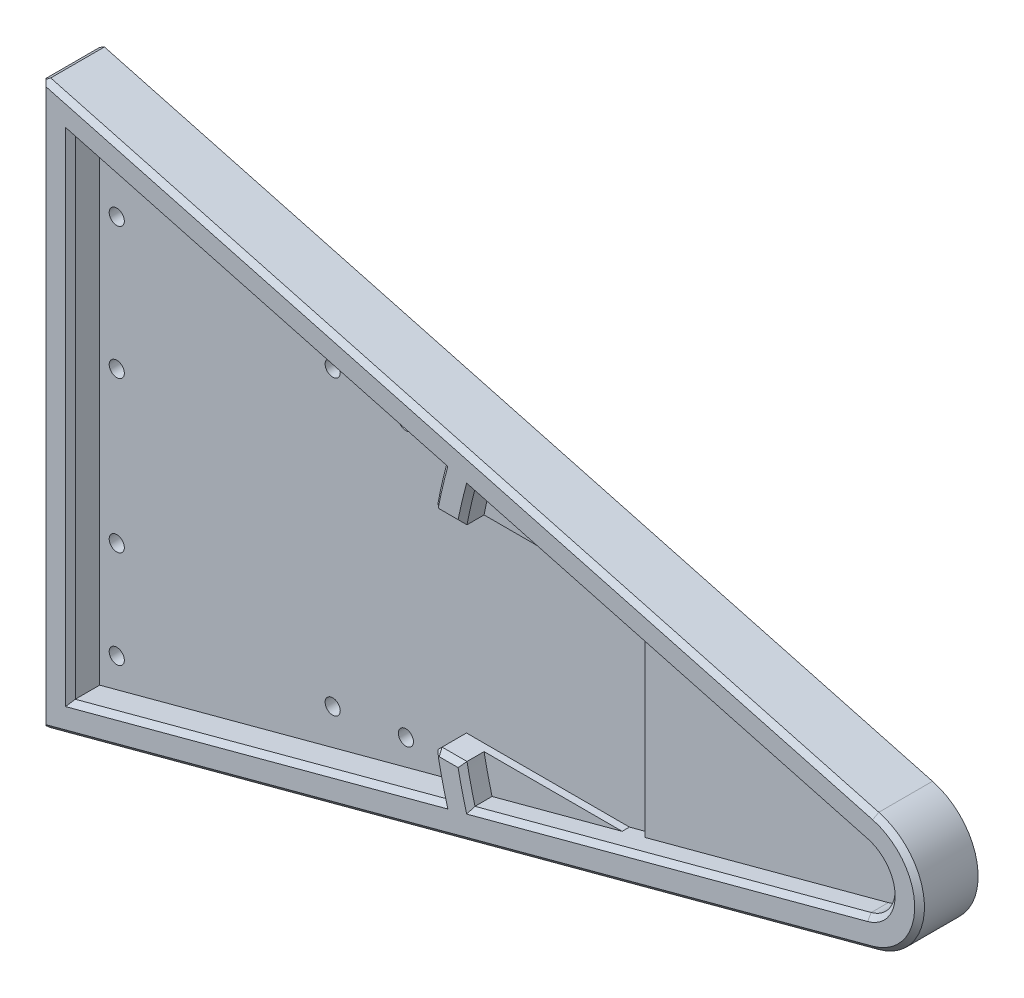
SolidWorks part; units mm, degrees
note: '?' marks a value the reader was unsure of. The reader was unsure of these and kept them because the rebuilt part matched: shared geometry of "Sketch3<3>".
ref_plane "Front Plane" through (0, 0, 0) normal (0, 0, 1) x (1, 0, 0)
ref_plane "Top Plane" through (0, 0, 0) normal (0, 1, 0) x (1, 0, 0)
ref_plane "Right Plane" through (0, 0, 0) normal (1, 0, 0) x (0, 0, -1)
sketch "Sketch3" plane through (0, 0, 0) normal (0, 0, 1) x (1, 0, 0)
  line L0 (1.6782, 6.263) -> (-79.3962, 27.9868) construction
  line L1 (-79.3962, -27.9868) -> (1.6782, -6.263) construction
  line L2 (-1.4973, 0) -> (-50001.4973, 0) construction
  line L3 (-79.4865, -28.1425) -> (1.711, -6.3857)
  line L4 (1.711, 6.3857) -> (-79.4865, 28.1425)
  line L6 (3.264, 12.1813) -> (-167.389, 57.9076)
  line L7 (3.264, 12.1813) -> (-83.598, 35.4558) construction
  line L8 (-83.598, -35.4558) -> (3.264, -12.1813) construction
  line L10 (3.264, -12.1813) -> (-83.598, -35.4558)
  line L11 (-167.389, -57.9076) -> (-83.598, -35.4558)
  line L12 (-161.389, -50.0882) -> (-85.1509, -29.6603)
  line L13 (-161.389, 50.0882) -> (-85.1509, 29.6603)
  line L14 (-167.389, 57.9076) -> (-167.389, -57.9076)
  line L15 (-159.0727, -55.6792) -> (-83.598, -35.4558) construction
  line L16 (-161.389, 50.0882) -> (-161.389, -50.0882)
  line L17 (-154.9085, -48.3518) -> (-85.1509, -29.6603) construction
  line L18 (-161.389, 57.9076) -> (-161.389, -57.9076) construction
  arc A0 (-79.3962, 27.9868) -> (-79.3962, -27.9868) centre (26.984, 0) ccw construction
  arc A1 (1.6782, -6.263) -> (1.6782, 6.263) centre (0, 0) ccw construction
  arc A2 (-79.4865, 28.1425) -> (-79.4865, -28.1425) centre (26.984, 0) ccw
  arc A3 (1.711, -6.3857) -> (1.711, 6.3857) centre (0, 0) ccw
  arc A4 (-85.2821, 29.6954) -> (-85.2821, -29.6954) centre (26.984, 0) ccw
  arc A5 (3.264, -12.1813) -> (3.264, 12.1813) centre (0, 0) ccw
  arc A8 (-154.9085, -48.3518) -> (-153.3259, 53.9546) centre (26.984, 0) cw construction
  arc A9 (-83.598, 35.4558) -> (-83.598, -35.4558) centre (26.984, 0) ccw construction
  arc A10 (-159.0727, -55.6792) -> (-159.0741, 55.6747) centre (26.984, 0) cw construction
  point P8 (-83.016, 0)
  point P24 (12.611, 0)
  dimension "D3" = 180
  dimension "D1" = 0.127
  dimension "D2" = 6
  dimension "D4" = 6
  dimension "D5" = 6
extrude "Boss-Extrude1" add sketch "Sketch3" along normal blind 6 contours L10 L11 L14 L6 A5
extrude "Boss-Extrude2" add sketch "Sketch3<3>" along normal blind 6 from surface at 6
sketch "Sketch3<3>" plane through (0, 0, 0) normal (0, 0, 1) x (1, 0, 0) same geometry as "Sketch3"
sketch "Sketch4" plane through (0, 0, 6) normal (0, 0, 1) x (1, 0, 0)
  line L11 (-52.8303, -21) -> (-81.1223, -21)
  line L12 (-49.0982, -20) -> (-79.0982, -20) construction
  line L13 (1.711, 6.3857) -> (-79.4865, 28.1425)
  line L14 (-79.4865, -28.1425) -> (1.711, -6.3857)
  line L15 (1.711, 6.3857) -> (-79.4865, 28.1425)
  line L16 (-79.4865, -28.1425) -> (1.711, -6.3857)
  line L17 (-49.0982, -20) -> (-49.0982, 20) construction
  line L18 (-49.0982, 20) -> (-79.0982, 20) construction
  line L19 (-79.0982, -20) -> (-79.0982, 20) construction
  line L20 (-49.0982, -20) -> (-79.0982, 20) construction
  line L21 (-49.0982, 20) -> (-79.0982, -20) construction
  line L22 (-48.0982, -19.7321) -> (-48.0982, 19.7321)
  line L23 (-52.8303, 21) -> (-81.1223, 21)
  line L24 (-48.0982, -21) -> (-79.0982, -21) construction
  line L25 (-48.0982, -21) -> (-48.0982, 21) construction
  line L26 (-48.0982, 21) -> (-79.0982, 21) construction
  arc A5 (1.711, -6.3857) -> (1.711, 6.3857) centre (0, 0) ccw
  arc A6 (-79.4865, 28.1425) -> (-79.4865, -28.1425) centre (26.984, 0) ccw
  arc A7 (1.711, -6.3857) -> (1.711, 6.3857) centre (0, 0) ccw
  arc A8 (-79.4865, 28.1425) -> (-79.4865, -28.1425) centre (26.984, 0) ccw
  point P16 (-64.0982, 0)
  arc M13 (1.711, -6.3857) -> (1.711, 6.3857) centre (0, 0) ccw
  line M14 (1.711, 6.3857) -> (-79.4865, 28.1425)
  arc M15 (-79.4865, 28.1425) -> (-79.4865, -28.1425) centre (26.984, 0) ccw
  line M16 (-79.4865, -28.1425) -> (1.711, -6.3857)
  dimension "D6" = 30
  dimension "D7" = 40
  dimension "D5" = 0
  dimension "D8" = 1
extrude "Boss-Extrude3" add sketch "Sketch4" along normal blind 1.5 contours L23 M14 M15 | L11 M16 M15 | L22 L16 M13 M14
sketch "Sketch5" plane through (0, 0, 6) normal (0, 0, 1) x (1, 0, 0)
  line L0 (0.52, 0) -> (-49999.48, 0) construction
  line L1 (-81.1223, 21) -> (-87.2285, 21)
  line L2 (-81.1223, -21) -> (-87.2285, -21)
  arc A0 (-85.2821, 29.6954) -> (-85.2821, -29.6954) centre (26.984, 0) ccw construction
  arc A1 (-85.2821, 29.6954) -> (-85.2821, -29.6954) centre (26.984, 0) ccw construction
  arc A2 (-81.1223, 21) -> (-81.1223, -21) centre (26.984, 0) ccw construction
  arc A3 (-87.2285, 21) -> (-87.2285, -21) centre (26.984, 0) ccw
  arc A4 (-81.1223, 21) -> (-81.1223, -21) centre (26.984, 0) ccw
extrude "Cut-Extrude3" cut sketch "Sketch5" along normal up to surface (6 mm away) up to face at (-79.7258, 0, 12)
chamfer "Chamfer1" distance 1 angle 45 2 edges at (-87.2285, -21, 9) (-87.2285, 21, 9)
chamfer "Chamfer2" distance 1 angle 45 18 edges at (-80.3638, -24.5849, 12) (-38.8877, -17.2641, 12) (6.611, 0, 12) (-38.8877, 17.2641, 12) (-80.3638, 24.5849, 12) (-83.7459, 21, 12) (-86.7069, 21.4893, 12) (-86.2289, 25.852, 12) (-123.3356, 39.8918, 12) (-123.3356, -39.8918, 12) (-86.2444, -25.7842, 12) (-86.6495, -21.421, 12) (-83.6754, -21, 12) (-82.0625, 35.0444, 12) (12.611, 0, 12) (-161.389, 0, 12) (-82.0625, -35.0444, 12) (-167.389, 0, 12)
sketch "Sketch6" plane through (0, 0, 6) normal (0, 0, 1) x (1, 0, 0)
  line L0 (0, 0) -> (-50000, 0) construction
  line L1 (-85.2821, 29.6954) -> (-161.389, 50.0882) construction
  line L3 (-117.513, -10.37) -> (-95.143, -10.37)
  line L4 (-117.513, -10.37) -> (-117.513, 10.37)
  line L5 (-117.513, 10.37) -> (-95.143, 10.37)
  line L6 (-95.143, -10.37) -> (-95.143, 10.37)
  line L7 (-117.513, -10.37) -> (-95.143, 10.37) construction
  line L8 (-117.513, 10.37) -> (-95.143, -10.37) construction
  line L9 (-117.513, 11.37) -> (-117.513, 32.11)
  line L10 (-117.513, 11.37) -> (-95.143, 11.37)
  line L11 (-95.143, 11.37) -> (-95.143, 32.11)
  line L12 (-117.513, 32.11) -> (-95.143, 32.11)
  line L13 (-117.513, -11.37) -> (-95.143, -11.37)
  line L14 (-95.143, -11.37) -> (-95.143, -32.11)
  line L15 (-117.513, -32.11) -> (-95.143, -32.11)
  line L16 (-117.513, -11.37) -> (-117.513, -32.11)
  arc A2 (-87.0704, -21.842) -> (-85.2821, -29.6954) centre (26.984, 0) ccw construction
  arc A3 (-85.2821, 29.6954) -> (-85.2821, -29.6954) centre (26.984, 0) ccw construction
  point P4 (-106.328, 0)
  point P10 (-89.143, 0)
  dimension "D1" = 22.37
  dimension "D2" = 20.74
  dimension "D3" = 6
  dimension "D4" = 2
  dimension "D5" = 1
chamfer "Chamfer3" distance 1 angle 45 2 edges at (-167.389, 57.9076, 5.5) (-167.389, -57.9076, 5.5)
ref_point "Point1"
ref_axis "Axis1" through (48.725, 0, 11) along (0, 0, -1)?
sketch "Sketch7" plane through (0, 0, 0) normal (0, 0, -1) x (-1, 0, 0)
  line L10 (161.389, 50.0882) -> (85.2821, 29.6954)
  line L11 (161.389, -50.0882) -> (161.389, 50.0882)
  line L12 (85.2821, -29.6954) -> (161.389, -50.0882)
  line L13 (86.2285, -21) -> (87.0704, -21.842)
  line L14 (52.8303, -21) -> (86.2285, -21)
  line L15 (48.0982, -19.7321) -> (52.8303, -21)
  line L16 (48.0982, 19.7321) -> (48.0982, -19.7321)
  line L17 (52.8303, 21) -> (48.0982, 19.7321)
  line L18 (86.3696, 21) -> (52.8303, 21)
  line L19 (87.0442, 21.9785) -> (86.3696, 21)
  line L20 (161.389, 50.0882) -> (85.2821, 29.6954)
  line L21 (161.389, -50.0882) -> (161.389, 50.0882)
  line L22 (85.2821, -29.6954) -> (161.389, -50.0882)
  arc A2 (85.2821, -29.6954) -> (87.0704, -21.842) centre (-26.984, 0) ccw
  arc A3 (87.0442, 21.9785) -> (85.2821, 29.6954) centre (-26.984, 0) ccw
  arc A5 (85.2821, -29.6954) -> (85.2821, 29.6954) centre (-26.984, 0) ccw
  dimension "D1" = 0
extrude "Cut-Extrude4" cut sketch "Sketch7" against normal blind 3
chamfer "Chamfer4" distance 1 angle 45 4 edges at (-123.3356, 39.8918, 3) (-161.389, 0, 3) (-123.3356, -39.8918, 3) (-89.143, 0, 3)
sketch "Sketch8" plane through (0, 0, 3) normal (0, 0, -1) x (-1, 0, 0)
  circle A0 centre (157.889, -43.1578) radius 1.95 construction
  circle A1 centre (157.889, -23.1578) radius 1.95 construction
  circle A2 centre (157.889, 7.7753) radius 1.95 construction
  circle A3 centre (157.889, 34.7753) radius 1.95 construction
  circle A4 centre (157.889, -43.1578) radius 1.95 construction
  circle A5 centre (157.889, -23.1578) radius 1.95 construction
  circle A6 centre (157.889, 7.7753) radius 1.95 construction
  circle A7 centre (157.889, 34.7753) radius 1.95 construction
  circle A8 centre (157.889, 34.7753) radius 1.55
  circle A9 centre (157.889, 7.7753) radius 1.55
  circle A10 centre (157.889, -23.1578) radius 1.55
  circle A11 centre (157.889, -43.1578) radius 1.55
  circle A12 centre (98.643, 28) radius 1.55
  circle A13 centre (113.643, 30) radius 1.55
  circle A14 centre (98.643, -28) radius 1.55
  circle A15 centre (113.643, -30) radius 1.55
  dimension "D1" = 3.1
extrude "Cut-Extrude5" cut sketch "Sketch8" against normal through all both and the other way through all
